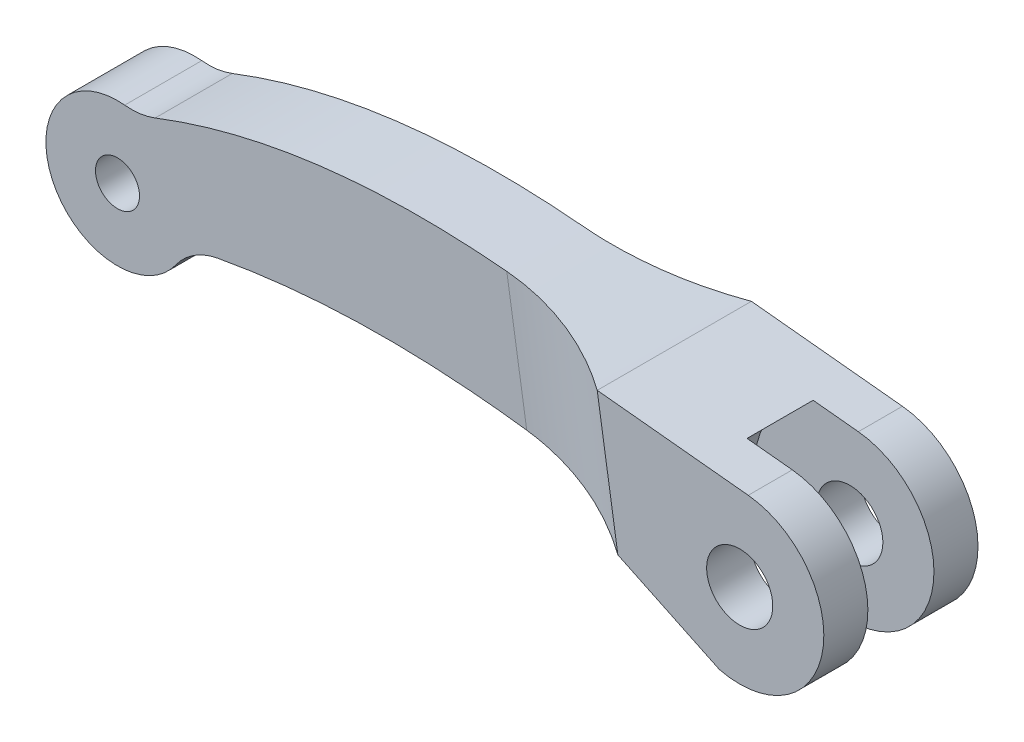
SolidWorks part; units mm, degrees
ref_plane "Спереди" through (0, 0, 0) normal (0, 0, 1) x (1, 0, 0)
ref_plane "Сверху" through (0, 0, 0) normal (0, 1, 0) x (1, 0, 0)
ref_plane "Справа" through (0, 0, 0) normal (1, 0, 0) x (0, 0, -1)
sketch "Sketch1" plane through (0, 0, 0) normal (0, 0, 1) x (1, 0, 0)
  line L2 (0, 0) -> (1, 0) construction
  line L3 (3.1038, -0.9691) -> (14.5105, 1.5965) construction
  line L4 (14.5105, 1.5965) -> (28.4491, -2.568) construction
  line L5 (0.9429, 3.1119) -> (12.7162, 8.0725) construction
  line L6 (12.7162, 8.0725) -> (29.5304, 2.963) construction
  circle A0 centre (0, 0) radius 1
  arc A2 (28.4491, -2.568) -> (29.5304, 2.963) centre (30, 0) ccw
  circle A3 centre (30, 0) radius 1.5
  arc A4 (0.9429, 3.1119) -> (3.1038, -0.9691) centre (0, 0) ccw
  spline S0 degree 2 poles (3.1038, -0.9691) (14.5105, 1.5965) (28.4491, -2.568) knots 0 0 0 1 1 1
  spline S1 degree 2 poles (0.9429, 3.1119) (12.7162, 8.0725) (29.5304, 2.963) knots 0 0 0 1 1 1
  dimension "D4" = 2
  dimension "D6" = 3
  dimension "D7" = 6
  dimension "D2" = 30
extrude "Boss-Extrude1" add sketch "Sketch1" along normal mid plane 3.5
fillet "Fillet1" radius 3 1 edges at (29.5304, 2.963, 0)
sketch "Sketch2" plane through (0, 0, 0) normal (0, 0, 1) x (1, 0, 0)
  line L0 (30.3874, 3.7998) -> (23.5309, 4.4988)
  line L1 (23.5309, 4.4988) -> (24.468, -1.5037)
  line L2 (24.468, -1.5037) -> (29.0737, -3.7055)
  circle A0 centre (30, 0) radius 1.5
  circle A1 centre (30, 0) radius 1.5 construction
  arc A2 (29.0737, -3.7055) -> (30.3874, 3.7998) centre (30, 0) ccw
  parabola Q0 (29.002, 3.1215) -> (0.9429, 3.1119) focus (5.6866, -10.5839) apex (-0.7735, 2.3218) construction
  parabola Q1 (3.1038, -0.9691) -> (28.4491, -2.568) focus (4.6731, -19.9146) apex (-1.8929, -2.4613) construction
  parabola Q2 (3.1038, -0.9691) -> (28.4491, -2.568) focus (4.6731, -19.9146) apex (-1.8929, -2.4613) construction
extrude "Boss-Extrude2" add sketch "Sketch2" along normal mid plane 7
sketch "Sketch3" plane through (0, 0, 0) normal (0, 0, 1) x (1, 0, 0)
  circle A0 centre (30, 0) radius 4.342
extrude "Cut-Extrude1" cut sketch "Sketch3" against normal mid plane 3
fillet "Fillet2" radius 10 2 edges at (23.9995, 1.4976, -1.75) (23.9995, 1.4976, 1.75)
fillet "Fillet3" radius 3 2 edges at (0.9429, 3.1119, 0) (3.1038, -0.9691, 0)
